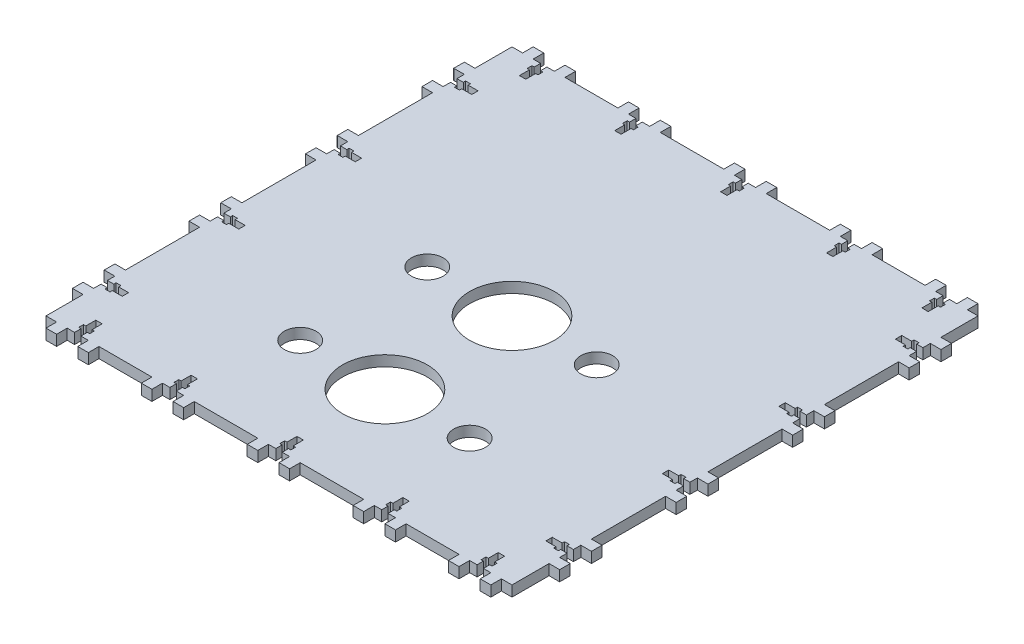
SolidWorks part; units mm, degrees
ref_plane "Front Plane" through (0, 0, 0) normal (0, 0, 1) x (1, 0, 0)
ref_plane "Top Plane" through (0, 0, 0) normal (0, 1, 0) x (1, 0, 0)
ref_plane "Right Plane" through (0, 0, 0) normal (1, 0, 0) x (0, 0, -1)
sketch "Sketch1" plane through (0, 0, 0) normal (0, 1, 0) x (1, 0, 0)
  line L0 (0, 0) -> (0, -110) construction
  line L1 (-110, -110) -> (110, -110)
  line L2 (-110, -110) -> (-110, 110)
  line L3 (-110, 110) -> (110, 110)
  line L4 (110, -110) -> (110, 110)
  line L5 (-110, -110) -> (110, 110) construction
  line L6 (-110, 110) -> (110, -110) construction
  line L7 (0, 0) -> (110, 0) construction
  line L8 (110, -30) -> (-110, -30) construction
  line L9 (-110, 72.5) -> (110, 72.5) construction
  line L10 (0, 0) -> (0, 98.7792) construction
  circle A0 centre (0, 0) radius 20
  circle A1 centre (40, 0) radius 7.5
  circle A2 centre (-40, 0) radius 7.5
  circle A3 centre (-40, -60) radius 7.5
  circle A4 centre (0, -60) radius 20
  circle A5 centre (40, -60) radius 7.5
  point P0 (0, 0)
  point P23 (-85.679, 72.5)
  point P27 (-71.9239, 72.5)
  point P28 (-61.1882, 72.5)
  line B0 (2.6, -107) -> (2.6, -104.7)
  line B1 (-1.5, -104.7) -> (-1.5, -100)
  line B2 (1.5, -100) -> (1.5, -104.7)
  line B3 (2.6, -104.7) -> (1.5, -104.7)
  line B4 (0, -110) -> (0, -98.7792) construction
  line B5 (1.5, -110) -> (5, -110)
  line B6 (5, -115) -> (10, -115)
  line B7 (10, -115) -> (10, -110)
  line B8 (5, -115) -> (5, -110)
  line B9 (-1.5, -110) -> (-5, -110)
  line B10 (-5, -110) -> (-5, -115)
  line B11 (-5, -115) -> (-10, -115)
  line B12 (-10, -115) -> (-10, -110)
  line B13 (-1.5, -100) -> (1.5, -100)
  line B14 (-1.5, -110) -> (-1.5, -107)
  line B15 (1.5, -107) -> (1.5, -110)
  line B16 (1.5, -110) -> (-1.5, -110) construction
  line B17 (-1.5, -104.7) -> (-2.6, -104.7)
  line B18 (-2.6, -107) -> (-1.5, -107)
  line B19 (1.5, -107) -> (2.6, -107)
  line B20 (-2.6, -104.7) -> (-2.6, -107)
  line B21 (0, -100) -> (0, -110) construction
  line B22 (52.6, -107) -> (52.6, -104.7)
  line B23 (48.5, -104.7) -> (48.5, -100)
  line B24 (51.5, -100) -> (51.5, -104.7)
  line B25 (52.6, -104.7) -> (51.5, -104.7)
  line B26 (50, -110) -> (50, -98.7792) construction
  line B27 (51.5, -110) -> (55, -110)
  line B28 (55, -115) -> (60, -115)
  line B29 (60, -115) -> (60, -110)
  line B30 (55, -115) -> (55, -110)
  line B31 (48.5, -110) -> (45, -110)
  line B32 (45, -110) -> (45, -115)
  line B33 (45, -115) -> (40, -115)
  line B34 (40, -115) -> (40, -110)
  line B35 (48.5, -100) -> (51.5, -100)
  line B36 (48.5, -110) -> (48.5, -107)
  line B37 (51.5, -107) -> (51.5, -110)
  line B38 (51.5, -110) -> (48.5, -110) construction
  line B39 (48.5, -104.7) -> (47.4, -104.7)
  line B40 (47.4, -107) -> (48.5, -107)
  line B41 (51.5, -107) -> (52.6, -107)
  line B42 (47.4, -104.7) -> (47.4, -107)
  line B43 (50, -100) -> (50, -110) construction
  line B44 (97.6, -107) -> (97.6, -104.7)
  line B45 (93.5, -104.7) -> (93.5, -100)
  line B46 (96.5, -100) -> (96.5, -104.7)
  line B47 (97.6, -104.7) -> (96.5, -104.7)
  line B48 (95, -110) -> (95, -98.7792) construction
  line B49 (96.5, -110) -> (100, -110)
  line B50 (100, -115) -> (105, -115)
  line B51 (105, -115) -> (105, -110)
  line B52 (100, -115) -> (100, -110)
  line B53 (93.5, -110) -> (90, -110)
  line B54 (90, -110) -> (90, -115)
  line B55 (90, -115) -> (85, -115)
  line B56 (85, -115) -> (85, -110)
  line B57 (93.5, -100) -> (96.5, -100)
  line B58 (93.5, -110) -> (93.5, -107)
  line B59 (96.5, -107) -> (96.5, -110)
  line B60 (96.5, -110) -> (93.5, -110) construction
  line B61 (93.5, -104.7) -> (92.4, -104.7)
  line B62 (92.4, -107) -> (93.5, -107)
  line B63 (96.5, -107) -> (97.6, -107)
  line B64 (92.4, -104.7) -> (92.4, -107)
  line B65 (95, -100) -> (95, -110) construction
  line B66 (107, -79.9) -> (104.7, -79.9)
  line B67 (104.7, -84) -> (100, -84)
  line B68 (100, -81) -> (104.7, -81)
  line B69 (104.7, -79.9) -> (104.7, -81)
  line B70 (110, -82.5) -> (98.7792, -82.5) construction
  line B71 (110, -81) -> (110, -77.5)
  line B72 (115, -77.5) -> (115, -72.5)
  line B73 (115, -72.5) -> (110, -72.5)
  line B74 (115, -77.5) -> (110, -77.5)
  line B75 (110, -84) -> (110, -87.5)
  line B76 (110, -87.5) -> (115, -87.5)
  line B77 (115, -87.5) -> (115, -92.5)
  line B78 (115, -92.5) -> (110, -92.5)
  line B79 (100, -84) -> (100, -81)
  line B80 (110, -84) -> (107, -84)
  line B81 (107, -81) -> (110, -81)
  line B82 (110, -81) -> (110, -84) construction
  line B83 (104.7, -84) -> (104.7, -85.1)
  line B84 (107, -85.1) -> (107, -84)
  line B85 (107, -81) -> (107, -79.9)
  line B86 (104.7, -85.1) -> (107, -85.1)
  line B87 (100, -82.5) -> (110, -82.5) construction
  line B88 (107, -24.9) -> (104.7, -24.9)
  line B89 (104.7, -29) -> (100, -29)
  line B90 (100, -26) -> (104.7, -26)
  line B91 (104.7, -24.9) -> (104.7, -26)
  line B92 (110, -27.5) -> (98.7792, -27.5) construction
  line B93 (110, -26) -> (110, -22.5)
  line B94 (115, -22.5) -> (115, -17.5)
  line B95 (115, -17.5) -> (110, -17.5)
  line B96 (115, -22.5) -> (110, -22.5)
  line B97 (110, -29) -> (110, -32.5)
  line B98 (110, -32.5) -> (115, -32.5)
  line B99 (115, -32.5) -> (115, -37.5)
  line B100 (115, -37.5) -> (110, -37.5)
  line B101 (100, -29) -> (100, -26)
  line B102 (110, -29) -> (107, -29)
  line B103 (107, -26) -> (110, -26)
  line B104 (110, -26) -> (110, -29) construction
  line B105 (104.7, -29) -> (104.7, -30.1)
  line B106 (107, -30.1) -> (107, -29)
  line B107 (107, -26) -> (107, -24.9)
  line B108 (104.7, -30.1) -> (107, -30.1)
  line B109 (100, -27.5) -> (110, -27.5) construction
  line B110 (-52.6, -107) -> (-52.6, -104.7)
  line B111 (-48.5, -104.7) -> (-48.5, -100)
  line B112 (-51.5, -100) -> (-51.5, -104.7)
  line B113 (-52.6, -104.7) -> (-51.5, -104.7)
  line B114 (-50, -110) -> (-50, -98.7792) construction
  line B115 (-51.5, -110) -> (-55, -110)
  line B116 (-55, -115) -> (-60, -115)
  line B117 (-60, -115) -> (-60, -110)
  line B118 (-55, -115) -> (-55, -110)
  line B119 (-48.5, -110) -> (-45, -110)
  line B120 (-45, -110) -> (-45, -115)
  line B121 (-45, -115) -> (-40, -115)
  line B122 (-40, -115) -> (-40, -110)
  line B123 (-48.5, -100) -> (-51.5, -100)
  line B124 (-48.5, -110) -> (-48.5, -107)
  line B125 (-51.5, -107) -> (-51.5, -110)
  line B126 (-51.5, -110) -> (-48.5, -110) construction
  line B127 (-48.5, -104.7) -> (-47.4, -104.7)
  line B128 (-47.4, -107) -> (-48.5, -107)
  line B129 (-51.5, -107) -> (-52.6, -107)
  line B130 (-47.4, -104.7) -> (-47.4, -107)
  line B131 (-50, -100) -> (-50, -110) construction
  line B132 (-97.6, -107) -> (-97.6, -104.7)
  line B133 (-93.5, -104.7) -> (-93.5, -100)
  line B134 (-96.5, -100) -> (-96.5, -104.7)
  line B135 (-97.6, -104.7) -> (-96.5, -104.7)
  line B136 (-95, -110) -> (-95, -98.7792) construction
  line B137 (-96.5, -110) -> (-100, -110)
  line B138 (-100, -115) -> (-105, -115)
  line B139 (-105, -115) -> (-105, -110)
  line B140 (-100, -115) -> (-100, -110)
  line B141 (-93.5, -110) -> (-90, -110)
  line B142 (-90, -110) -> (-90, -115)
  line B143 (-90, -115) -> (-85, -115)
  line B144 (-85, -115) -> (-85, -110)
  line B145 (-93.5, -100) -> (-96.5, -100)
  line B146 (-93.5, -110) -> (-93.5, -107)
  line B147 (-96.5, -107) -> (-96.5, -110)
  line B148 (-96.5, -110) -> (-93.5, -110) construction
  line B149 (-93.5, -104.7) -> (-92.4, -104.7)
  line B150 (-92.4, -107) -> (-93.5, -107)
  line B151 (-96.5, -107) -> (-97.6, -107)
  line B152 (-92.4, -104.7) -> (-92.4, -107)
  line B153 (-95, -100) -> (-95, -110) construction
  line B154 (52.6, 107) -> (52.6, 104.7)
  line B155 (48.5, 104.7) -> (48.5, 100)
  line B156 (51.5, 100) -> (51.5, 104.7)
  line B157 (52.6, 104.7) -> (51.5, 104.7)
  line B158 (50, 110) -> (50, 98.7792) construction
  line B159 (51.5, 110) -> (55, 110)
  line B160 (55, 115) -> (60, 115)
  line B161 (60, 115) -> (60, 110)
  line B162 (55, 115) -> (55, 110)
  line B163 (48.5, 110) -> (45, 110)
  line B164 (45, 110) -> (45, 115)
  line B165 (45, 115) -> (40, 115)
  line B166 (40, 115) -> (40, 110)
  line B167 (48.5, 100) -> (51.5, 100)
  line B168 (48.5, 110) -> (48.5, 107)
  line B169 (51.5, 107) -> (51.5, 110)
  line B170 (51.5, 110) -> (48.5, 110) construction
  line B171 (48.5, 104.7) -> (47.4, 104.7)
  line B172 (47.4, 107) -> (48.5, 107)
  line B173 (51.5, 107) -> (52.6, 107)
  line B174 (47.4, 104.7) -> (47.4, 107)
  line B175 (50, 100) -> (50, 110) construction
  line B176 (2.6, 107) -> (2.6, 104.7)
  line B177 (-1.5, 104.7) -> (-1.5, 100)
  line B178 (1.5, 100) -> (1.5, 104.7)
  line B179 (2.6, 104.7) -> (1.5, 104.7)
  line B180 (0, 110) -> (0, 98.7792) construction
  line B181 (1.5, 110) -> (5, 110)
  line B182 (5, 115) -> (10, 115)
  line B183 (10, 115) -> (10, 110)
  line B184 (5, 115) -> (5, 110)
  line B185 (-1.5, 110) -> (-5, 110)
  line B186 (-5, 110) -> (-5, 115)
  line B187 (-5, 115) -> (-10, 115)
  line B188 (-10, 115) -> (-10, 110)
  line B189 (-1.5, 100) -> (1.5, 100)
  line B190 (-1.5, 110) -> (-1.5, 107)
  line B191 (1.5, 107) -> (1.5, 110)
  line B192 (1.5, 110) -> (-1.5, 110) construction
  line B193 (-1.5, 104.7) -> (-2.6, 104.7)
  line B194 (-2.6, 107) -> (-1.5, 107)
  line B195 (1.5, 107) -> (2.6, 107)
  line B196 (-2.6, 104.7) -> (-2.6, 107)
  line B197 (0, 100) -> (0, 110) construction
  line B198 (97.6, 107) -> (97.6, 104.7)
  line B199 (93.5, 104.7) -> (93.5, 100)
  line B200 (96.5, 100) -> (96.5, 104.7)
  line B201 (97.6, 104.7) -> (96.5, 104.7)
  line B202 (95, 110) -> (95, 98.7792) construction
  line B203 (96.5, 110) -> (100, 110)
  line B204 (100, 115) -> (105, 115)
  line B205 (105, 115) -> (105, 110)
  line B206 (100, 115) -> (100, 110)
  line B207 (93.5, 110) -> (90, 110)
  line B208 (90, 110) -> (90, 115)
  line B209 (90, 115) -> (85, 115)
  line B210 (85, 115) -> (85, 110)
  line B211 (93.5, 100) -> (96.5, 100)
  line B212 (93.5, 110) -> (93.5, 107)
  line B213 (96.5, 107) -> (96.5, 110)
  line B214 (96.5, 110) -> (93.5, 110) construction
  line B215 (93.5, 104.7) -> (92.4, 104.7)
  line B216 (92.4, 107) -> (93.5, 107)
  line B217 (96.5, 107) -> (97.6, 107)
  line B218 (92.4, 104.7) -> (92.4, 107)
  line B219 (95, 100) -> (95, 110) construction
  line B220 (-52.6, 107) -> (-52.6, 104.7)
  line B221 (-48.5, 104.7) -> (-48.5, 100)
  line B222 (-51.5, 100) -> (-51.5, 104.7)
  line B223 (-52.6, 104.7) -> (-51.5, 104.7)
  line B224 (-50, 110) -> (-50, 98.7792) construction
  line B225 (-51.5, 110) -> (-55, 110)
  line B226 (-55, 115) -> (-60, 115)
  line B227 (-60, 115) -> (-60, 110)
  line B228 (-55, 115) -> (-55, 110)
  line B229 (-48.5, 110) -> (-45, 110)
  line B230 (-45, 110) -> (-45, 115)
  line B231 (-45, 115) -> (-40, 115)
  line B232 (-40, 115) -> (-40, 110)
  line B233 (-48.5, 100) -> (-51.5, 100)
  line B234 (-48.5, 110) -> (-48.5, 107)
  line B235 (-51.5, 107) -> (-51.5, 110)
  line B236 (-51.5, 110) -> (-48.5, 110) construction
  line B237 (-48.5, 104.7) -> (-47.4, 104.7)
  line B238 (-47.4, 107) -> (-48.5, 107)
  line B239 (-51.5, 107) -> (-52.6, 107)
  line B240 (-47.4, 104.7) -> (-47.4, 107)
  line B241 (-50, 100) -> (-50, 110) construction
  line B242 (-97.6, 107) -> (-97.6, 104.7)
  line B243 (-93.5, 104.7) -> (-93.5, 100)
  line B244 (-96.5, 100) -> (-96.5, 104.7)
  line B245 (-97.6, 104.7) -> (-96.5, 104.7)
  line B246 (-95, 110) -> (-95, 98.7792) construction
  line B247 (-96.5, 110) -> (-100, 110)
  line B248 (-100, 115) -> (-105, 115)
  line B249 (-105, 115) -> (-105, 110)
  line B250 (-100, 115) -> (-100, 110)
  line B251 (-93.5, 110) -> (-90, 110)
  line B252 (-90, 110) -> (-90, 115)
  line B253 (-90, 115) -> (-85, 115)
  line B254 (-85, 115) -> (-85, 110)
  line B255 (-93.5, 100) -> (-96.5, 100)
  line B256 (-93.5, 110) -> (-93.5, 107)
  line B257 (-96.5, 107) -> (-96.5, 110)
  line B258 (-96.5, 110) -> (-93.5, 110) construction
  line B259 (-93.5, 104.7) -> (-92.4, 104.7)
  line B260 (-92.4, 107) -> (-93.5, 107)
  line B261 (-96.5, 107) -> (-97.6, 107)
  line B262 (-92.4, 104.7) -> (-92.4, 107)
  line B263 (-95, 100) -> (-95, 110) construction
  line B264 (107, 79.9) -> (104.7, 79.9)
  line B265 (104.7, 84) -> (100, 84)
  line B266 (100, 81) -> (104.7, 81)
  line B267 (104.7, 79.9) -> (104.7, 81)
  line B268 (110, 82.5) -> (98.7792, 82.5) construction
  line B269 (110, 81) -> (110, 77.5)
  line B270 (115, 77.5) -> (115, 72.5)
  line B271 (115, 72.5) -> (110, 72.5)
  line B272 (115, 77.5) -> (110, 77.5)
  line B273 (110, 84) -> (110, 87.5)
  line B274 (110, 87.5) -> (115, 87.5)
  line B275 (115, 87.5) -> (115, 92.5)
  line B276 (115, 92.5) -> (110, 92.5)
  line B277 (100, 84) -> (100, 81)
  line B278 (110, 84) -> (107, 84)
  line B279 (107, 81) -> (110, 81)
  line B280 (110, 81) -> (110, 84) construction
  line B281 (104.7, 84) -> (104.7, 85.1)
  line B282 (107, 85.1) -> (107, 84)
  line B283 (107, 81) -> (107, 79.9)
  line B284 (104.7, 85.1) -> (107, 85.1)
  line B285 (100, 82.5) -> (110, 82.5) construction
  line B286 (107, 24.9) -> (104.7, 24.9)
  line B287 (104.7, 29) -> (100, 29)
  line B288 (100, 26) -> (104.7, 26)
  line B289 (104.7, 24.9) -> (104.7, 26)
  line B290 (110, 27.5) -> (98.7792, 27.5) construction
  line B291 (110, 26) -> (110, 22.5)
  line B292 (115, 22.5) -> (115, 17.5)
  line B293 (115, 17.5) -> (110, 17.5)
  line B294 (115, 22.5) -> (110, 22.5)
  line B295 (110, 29) -> (110, 32.5)
  line B296 (110, 32.5) -> (115, 32.5)
  line B297 (115, 32.5) -> (115, 37.5)
  line B298 (115, 37.5) -> (110, 37.5)
  line B299 (100, 29) -> (100, 26)
  line B300 (110, 29) -> (107, 29)
  line B301 (107, 26) -> (110, 26)
  line B302 (110, 26) -> (110, 29) construction
  line B303 (104.7, 29) -> (104.7, 30.1)
  line B304 (107, 30.1) -> (107, 29)
  line B305 (107, 26) -> (107, 24.9)
  line B306 (104.7, 30.1) -> (107, 30.1)
  line B307 (100, 27.5) -> (110, 27.5) construction
  line B308 (-107, -79.9) -> (-104.7, -79.9)
  line B309 (-104.7, -84) -> (-100, -84)
  line B310 (-100, -81) -> (-104.7, -81)
  line B311 (-104.7, -79.9) -> (-104.7, -81)
  line B312 (-110, -82.5) -> (-98.7792, -82.5) construction
  line B313 (-110, -81) -> (-110, -77.5)
  line B314 (-115, -77.5) -> (-115, -72.5)
  line B315 (-115, -72.5) -> (-110, -72.5)
  line B316 (-115, -77.5) -> (-110, -77.5)
  line B317 (-110, -84) -> (-110, -87.5)
  line B318 (-110, -87.5) -> (-115, -87.5)
  line B319 (-115, -87.5) -> (-115, -92.5)
  line B320 (-115, -92.5) -> (-110, -92.5)
  line B321 (-100, -84) -> (-100, -81)
  line B322 (-110, -84) -> (-107, -84)
  line B323 (-107, -81) -> (-110, -81)
  line B324 (-110, -81) -> (-110, -84) construction
  line B325 (-104.7, -84) -> (-104.7, -85.1)
  line B326 (-107, -85.1) -> (-107, -84)
  line B327 (-107, -81) -> (-107, -79.9)
  line B328 (-104.7, -85.1) -> (-107, -85.1)
  line B329 (-100, -82.5) -> (-110, -82.5) construction
  line B330 (-107, 79.9) -> (-104.7, 79.9)
  line B331 (-104.7, 84) -> (-100, 84)
  line B332 (-100, 81) -> (-104.7, 81)
  line B333 (-104.7, 79.9) -> (-104.7, 81)
  line B334 (-110, 82.5) -> (-98.7792, 82.5) construction
  line B335 (-110, 81) -> (-110, 77.5)
  line B336 (-115, 77.5) -> (-115, 72.5)
  line B337 (-115, 72.5) -> (-110, 72.5)
  line B338 (-115, 77.5) -> (-110, 77.5)
  line B339 (-110, 84) -> (-110, 87.5)
  line B340 (-110, 87.5) -> (-115, 87.5)
  line B341 (-115, 87.5) -> (-115, 92.5)
  line B342 (-115, 92.5) -> (-110, 92.5)
  line B343 (-100, 84) -> (-100, 81)
  line B344 (-110, 84) -> (-107, 84)
  line B345 (-107, 81) -> (-110, 81)
  line B346 (-110, 81) -> (-110, 84) construction
  line B347 (-104.7, 84) -> (-104.7, 85.1)
  line B348 (-107, 85.1) -> (-107, 84)
  line B349 (-107, 81) -> (-107, 79.9)
  line B350 (-104.7, 85.1) -> (-107, 85.1)
  line B351 (-100, 82.5) -> (-110, 82.5) construction
  line B352 (-107, 24.9) -> (-104.7, 24.9)
  line B353 (-104.7, 29) -> (-100, 29)
  line B354 (-100, 26) -> (-104.7, 26)
  line B355 (-104.7, 24.9) -> (-104.7, 26)
  line B356 (-110, 27.5) -> (-98.7792, 27.5) construction
  line B357 (-110, 26) -> (-110, 22.5)
  line B358 (-115, 22.5) -> (-115, 17.5)
  line B359 (-115, 17.5) -> (-110, 17.5)
  line B360 (-115, 22.5) -> (-110, 22.5)
  line B361 (-110, 29) -> (-110, 32.5)
  line B362 (-110, 32.5) -> (-115, 32.5)
  line B363 (-115, 32.5) -> (-115, 37.5)
  line B364 (-115, 37.5) -> (-110, 37.5)
  line B365 (-100, 29) -> (-100, 26)
  line B366 (-110, 29) -> (-107, 29)
  line B367 (-107, 26) -> (-110, 26)
  line B368 (-110, 26) -> (-110, 29) construction
  line B369 (-104.7, 29) -> (-104.7, 30.1)
  line B370 (-107, 30.1) -> (-107, 29)
  line B371 (-107, 26) -> (-107, 24.9)
  line B372 (-104.7, 30.1) -> (-107, 30.1)
  line B373 (-100, 27.5) -> (-110, 27.5) construction
  line B374 (-107, -24.9) -> (-104.7, -24.9)
  line B375 (-104.7, -29) -> (-100, -29)
  line B376 (-100, -26) -> (-104.7, -26)
  line B377 (-104.7, -24.9) -> (-104.7, -26)
  line B378 (-110, -27.5) -> (-98.7792, -27.5) construction
  line B379 (-110, -26) -> (-110, -22.5)
  line B380 (-115, -22.5) -> (-115, -17.5)
  line B381 (-115, -17.5) -> (-110, -17.5)
  line B382 (-115, -22.5) -> (-110, -22.5)
  line B383 (-110, -29) -> (-110, -32.5)
  line B384 (-110, -32.5) -> (-115, -32.5)
  line B385 (-115, -32.5) -> (-115, -37.5)
  line B386 (-115, -37.5) -> (-110, -37.5)
  line B387 (-100, -29) -> (-100, -26)
  line B388 (-110, -29) -> (-107, -29)
  line B389 (-107, -26) -> (-110, -26)
  line B390 (-110, -26) -> (-110, -29) construction
  line B391 (-104.7, -29) -> (-104.7, -30.1)
  line B392 (-107, -30.1) -> (-107, -29)
  line B393 (-107, -26) -> (-107, -24.9)
  line B394 (-104.7, -30.1) -> (-107, -30.1)
  line B395 (-100, -27.5) -> (-110, -27.5) construction
  dimension "D7" = 40
  dimension "D8" = 15
  dimension "D1" = 220
  dimension "D2" = 220
  dimension "D3" = 50
  dimension "D4" = 45
  dimension "D5" = 27.5
  dimension "D6" = 82.5
  dimension "D9" = 40
  dimension "D10" = 30
sketch_block_instance "Insert M3 plots ep 5mm-4"
sketch_block "Insert M3 plots ep 5mm" parameters "D1"=10, "D2"=5, "D3"=5
sketch_block_instance "Decoupe Insert M3-4"
sketch_block "Decoupe Insert M3" parameters "D1"=5.2, "D2"=3, "D3"=2.3, "D4"=3, "D5"=10
sketch_block_instance "Insert M3 plots ep 5mm-5"
sketch_block_instance "Insert M3 plots ep 5mm-6"
sketch_block_instance "Insert M3 plots ep 5mm-7"
sketch_block_instance "Insert M3 plots ep 5mm-9"
sketch_block_instance "Insert M3 plots ep 5mm-10"
sketch_block_instance "Insert M3 plots ep 5mm-11"
sketch_block_instance "Insert M3 plots ep 5mm-12"
sketch_block_instance "Insert M3 plots ep 5mm-13"
sketch_block_instance "Insert M3 plots ep 5mm-14"
sketch_block_instance "Insert M3 plots ep 5mm-15"
sketch_block_instance "Insert M3 plots ep 5mm-16"
sketch_block_instance "Insert M3 plots ep 5mm-17"
sketch_block_instance "Insert M3 plots ep 5mm-18"
sketch_block_instance "Insert M3 plots ep 5mm-19"
sketch_block_instance "Insert M3 plots ep 5mm-20"
sketch_block_instance "Insert M3 plots ep 5mm-21"
sketch_block_instance "Insert M3 plots ep 5mm-22"
extrude "Boss-Extrude1" add sketch "Sketch1" along normal blind 5 contours B143 B144 L1 B142 | B138 B140 L1 B139 | B319 B320 L2 B318 | B314 B316 L2 B315 | B380 B382 L2 B381 | B385 B386 L2 B384 | B364 B363 B362 L2 | B360 B358 B359 L2 | B338 B336 B337 L2 | B342 B341 B340 L2 | B250 B248 B249 L3 | B254 B253 B252 L3 | B228 B226 B227 L3 | B232 B231 B230 L3 | B187 B188 L3 B186 | B182 B184 L3 B183 | B165 B166 L3 B164 | B160 B162 L3 B161 | B209 B210 L3 B208 | B204 B206 L3 B205 | B275 B276 L4 B274 | B270 B272 L4 B271 | B121 B122 L1 B120 | B116 B118 L1 B117 | B12 B11 B10 L1 | B8 B6 B7 L1 | B34 B33 B32 L1 | B30 B28 B29 L1 | B56 B55 B54 L1 | B52 B50 B51 L1 | B78 B77 B76 L4 | B74 B72 B73 L4 | B100 B99 B98 L4 | B96 B94 B95 L4 | B292 B294 L4 B293 | B297 B298 L4 B296 | B389 B393 B374 B377 B376 B387 B375 B391 B394 B392 B388 L2 B323 B327 B308 B311 B310 B321 B309 B325 B328 B326 B322 L1 B147 B151 B132 B135 B134 B145 B133 B149 B152 B150 B146 B125 B129 region at (-106.8887, 0, 101.25) region at (-102.5, 0, 112.5) region at (-112.5, 0, 90) region at (-87.5, 0, 112.5) region at (-112.5, 0, 75) region at (-57.5, 0, 112.5) region at (-112.5, 0, 35) region at (-42.5, 0, 112.5) region at (-112.5, 0, 20) region at (-7.5, 0, 112.5) region at (-112.5, 0, -20) region at (7.5, 0, 112.5) region at (-112.5, 0, -35) region at (42.5, 0, 112.5) region at (-112.5, 0, -75) region at (57.5, 0, 112.5) region at (-112.5, 0, -90) region at (87.5, 0, 112.5) region at (-102.5, 0, -112.5) region at (102.5, 0, 112.5) region at (-87.5, 0, -112.5) region at (112.5, 0, 90) region at (-57.5, 0, -112.5) region at (112.5, 0, 75) region at (-42.5, 0, -112.5) region at (112.5, 0, 35) region at (-7.5, 0, -112.5) region at (112.5, 0, 20) region at (7.5, 0, -112.5) region at (112.5, 0, -20) region at (42.5, 0, -112.5) region at (112.5, 0, -35) region at (57.5, 0, -112.5) region at (112.5, 0, -75) region at (87.5, 0, -112.5) region at (112.5, 0, -90) region at (102.5, 0, -112.5)
sketch "Sketch3" plane through (0, 5, 0) normal (0, 1, 0) x (1, 0, 0)
  line L0 (-110, 55) -> (110, 55) construction
  line L1 (-110, 37.5) -> (-110, 72.5) construction
  line L2 (110, 37.5) -> (110, 72.5) construction
  text T0 "<b>Кирилл</b> <i>2000</i>" font "Century Gothic" height 20
  point P7 (0, 0)
